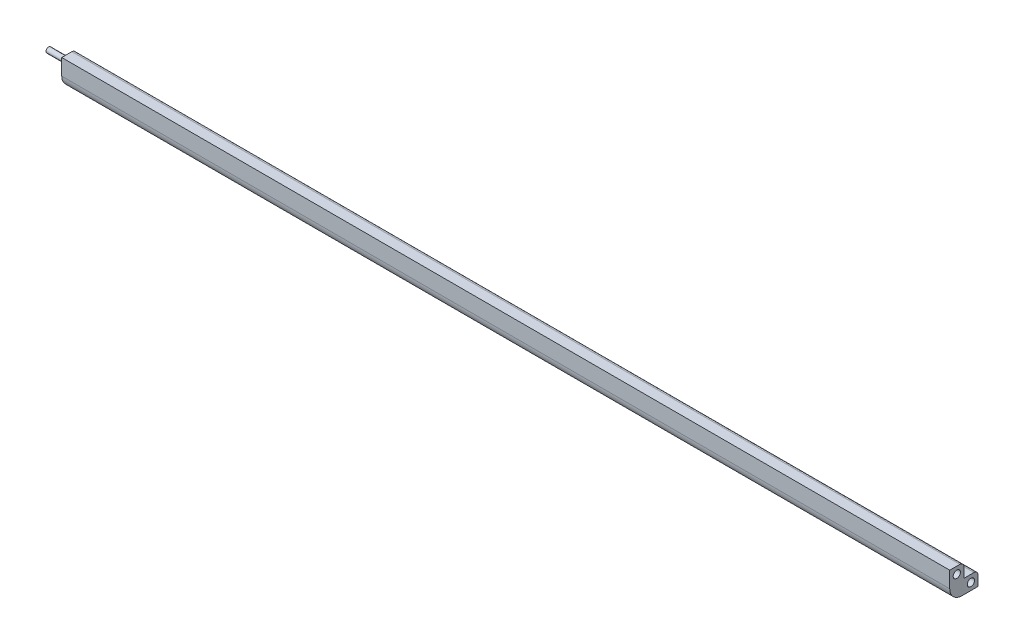
SolidWorks part; units mm, degrees
ref_plane "Front Plane" through (0, 0, 0) normal (0, 0, 1) x (1, 0, 0)
ref_plane "Top Plane" through (0, 0, 0) normal (0, 1, 0) x (1, 0, 0)
ref_plane "Right Plane" through (0, 0, 0) normal (1, 0, 0) x (0, 0, -1)
sketch "Sketch1" plane through (-29.2126, 0, 0) normal (1, 0, 0) x (0, 0, -1)
  line L1 (11.4452, 34.4708) -> (4.4452, 34.4708)
  line L2 (-25.0548, 34.4708) -> (6.4452, 34.4708) construction
  line L3 (4.4452, 34.4708) -> (4.4452, 27.4708)
  line L4 (4.4452, 27.4708) -> (11.4452, 27.4708)
  line L5 (11.4452, 29.4708) -> (11.4452, -36.5292) construction
  line L7 (11.4452, 27.4708) -> (11.4452, 34.4708)
  line L8 (7.9452, 34.4708) -> (7.9452, 30.9708)
  line L9 (7.9452, 30.9708) -> (11.4452, 30.9708)
  circle A0 centre (6.1952, 32.7208) radius 0.65
  circle A1 centre (9.6952, 29.2208) radius 0.65
  circle A2 centre (6.1952, 32.7208) radius 0.9
  circle A3 centre (9.6952, 29.2208) radius 0.9
  line M11 (11.4452, -36.5292) -> (11.4452, 29.4708)
  arc M12 (11.4452, 29.4708) -> (6.4452, 34.4708) centre (6.4452, 29.4708) ccw
  line M13 (6.4452, 34.4708) -> (-25.0548, 34.4708)
  dimension "D5" = 1.3
  dimension "D6" = 1.8
  dimension "D7" = 1.3
  dimension "D8" = 1.8
  dimension "D1" = 7
  dimension "D2" = 7
  dimension "D3" = 1.75
  dimension "D4" = 1.75
  dimension "D9" = 1.75
  dimension "D10" = 1.75
extrude "Boss-Extrude1" add sketch "Sketch1" along normal blind 220 contours L9 L8 L3 L4 A3 A2 M12 M13 M11 | L9 L7 M12 | L8 L1 M12 | A0 | A2 A0 | A3 A1 | A1 region at (-29.2126, 34.402, -7.5719) region at (-29.2126, 30.5975, -11.3764) region at (-29.2126, 30.2777, -7.2521) region at (-29.2126, 32.7208, -6.1952) region at (-29.2126, 29.2208, -9.6952) region at (-29.2126, 32.7208, -5.3206) region at (-29.2126, 29.2208, -8.8206)
sketch "Sketch2" plane through (190.7874, 0, 0) normal (1, 0, 0) x (0, 0, -1)
  line L0 (11.4452, 34.4708) -> (4.4452, 34.4708)
  line L1 (4.4452, 34.4708) -> (4.4452, 27.4708)
  line L2 (4.4452, 27.4708) -> (11.4452, 27.4708)
  line L3 (11.4452, 27.4708) -> (11.4452, 34.4708)
  line L4 (7.9452, 34.4708) -> (7.9452, 30.9708)
  line L5 (7.9452, 30.9708) -> (11.4452, 30.9708)
  line L6 (7.9452, 34.4708) -> (4.4452, 34.4708) construction
  line L7 (-25.0548, 34.4708) -> (6.4452, 34.4708) construction
  line L8 (11.4452, 27.4708) -> (11.4452, 30.9708) construction
  circle A0 centre (6.1952, 32.7208) radius 0.65
  circle A1 centre (9.6952, 29.2208) radius 0.65
  circle A2 centre (6.1952, 32.7208) radius 0.9
  circle A3 centre (9.6952, 29.2208) radius 0.9
  dimension "D5" = 1.3
  dimension "D6" = 1.8
  dimension "D7" = 1.3
  dimension "D8" = 1.8
  dimension "D1" = 7
  dimension "D2" = 7
  dimension "D3" = 1.75
  dimension "D4" = 1.75
  dimension "D9" = 1.75
  dimension "D10" = 1.75
extrude "Cut-Extrude1" cut sketch "Sketch2" against normal blind 6 contours A2 A0 | A0 | A3 A1 | A1 | A3 region at (190.7874, 32.7208, -6.1952) region at (190.7874, 29.2208, -9.6952) region at (190.7874, 32.7208, -5.3206) region at (190.7874, 29.2208, -8.8206)
extrude "Boss-Extrude2" add sketch "Sketch1<3>" against normal blind 5 contours A0 | A1 region at (-29.2126, 32.7208, -6.1952) region at (-29.2126, 29.2208, -9.6952)
sketch "Sketch1<3>" plane through (-29.2126, 0, 0) normal (1, 0, 0) x (0, 0, -1) same geometry as "Sketch1"
fillet "Fillet1" radius 3 1 edges at (80.7874, 27.4708, -4.4452)
fillet "Fillet2" radius 1 2 edges at (80.7874, 30.9708, -11.4452) (80.7874, 34.4708, -7.9452)
